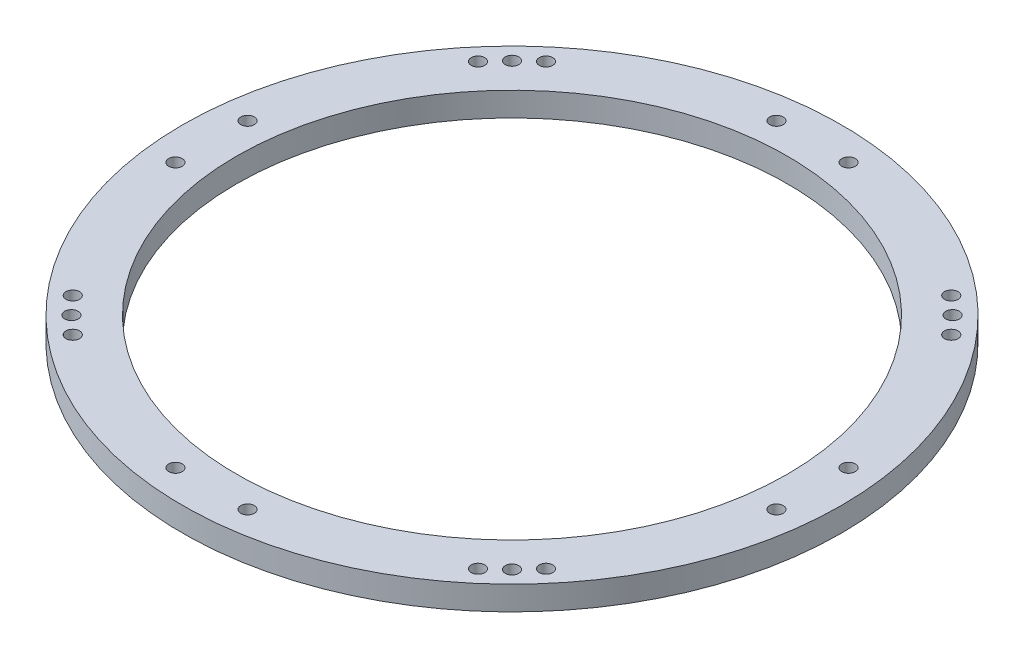
SolidWorks part; units mm, degrees
material "Oak"
ref_plane "Front Plane" through (0, 0, 0) normal (0, 0, 1) x (1, 0, 0)
ref_plane "Top Plane" through (0, 0, 0) normal (0, 1, 0) x (1, 0, 0)
ref_plane "Right Plane" through (0, 0, 0) normal (1, 0, 0) x (0, 0, -1)
sketch "Sketch1" plane through (0, 0, 0) normal (0, 0, 1) x (1, 0, 0)
  line L0 (0, -200000) -> (0, 218797.9879) construction
  line L5 (0, -200000) -> (0, 218797.9879) construction
  line L6 (174.1012, 206.3724) -> (174.1012, 193.6724)
  line L7 (145.5262, 206.3724) -> (174.1012, 206.3724)
  line L8 (174.1012, 193.6724) -> (145.5262, 193.6724)
  line L9 (145.5262, 193.6724) -> (145.5262, 206.3724)
revolve "Revolve1" add sketch "Sketch1" angle 360 about L5
hole_wizard "9/32 (0.28125) Diameter Hole1" positions "Sketch5" profile "Sketch6" hole size "9/32" standard "ANSI Inch" end condition through all
sketch "Sketch5" plane through (0, 206.3724, 0) normal (0, 1, 0) x (1, 0, 0)
  point P0 (-116.373, 116.373)
  point P3 (-107.0457, 125.0062)
  point P6 (-125.0062, 107.0457)
sketch "Sketch6" plane through (-116.373, 206.3724, -116.373) normal (1, 0, 0) x (0, 0, 1)
  line L0 (0, 0) -> (0, 12.7)
  line L1 (0, 12.7) -> (3.5719, 12.7)
  line L2 (3.5719, 12.7) -> (3.5719, 0)
  line L5 (3.5719, 0) -> (0, 0)
  line L11 (0, -6.35) -> (0, 107.95) construction
  dimension "Thru Hole Dia." = 7.1437
  dimension "Thru Hole Depth" = 12.7
sketch "Sketch7" plane through (0, 206.3724, 0) normal (0, 1, 0) x (1, 0, 0)
  line L0 (0, 0) -> (158.75, 0) construction
  line L1 (158.75, 19.05) -> (158.75, -19.05) construction
  circle A0 centre (158.75, -19.05) radius 3.5719
  circle A1 centre (158.75, 19.05) radius 3.5719
  point P6 (158.75, 0)
  dimension "D3" = 7.1437
  dimension "D1" = 38.1
  dimension "D2" = 158.75
extrude "Cut-Extrude1" cut sketch "Sketch7" against normal through all
pattern_circular "CirPattern1" count 4 over 360 about axis through (0, -200000, 0) along (0, -1, 0) of "9/32 (0.28125) Diameter Hole1", "Cut-Extrude1"
